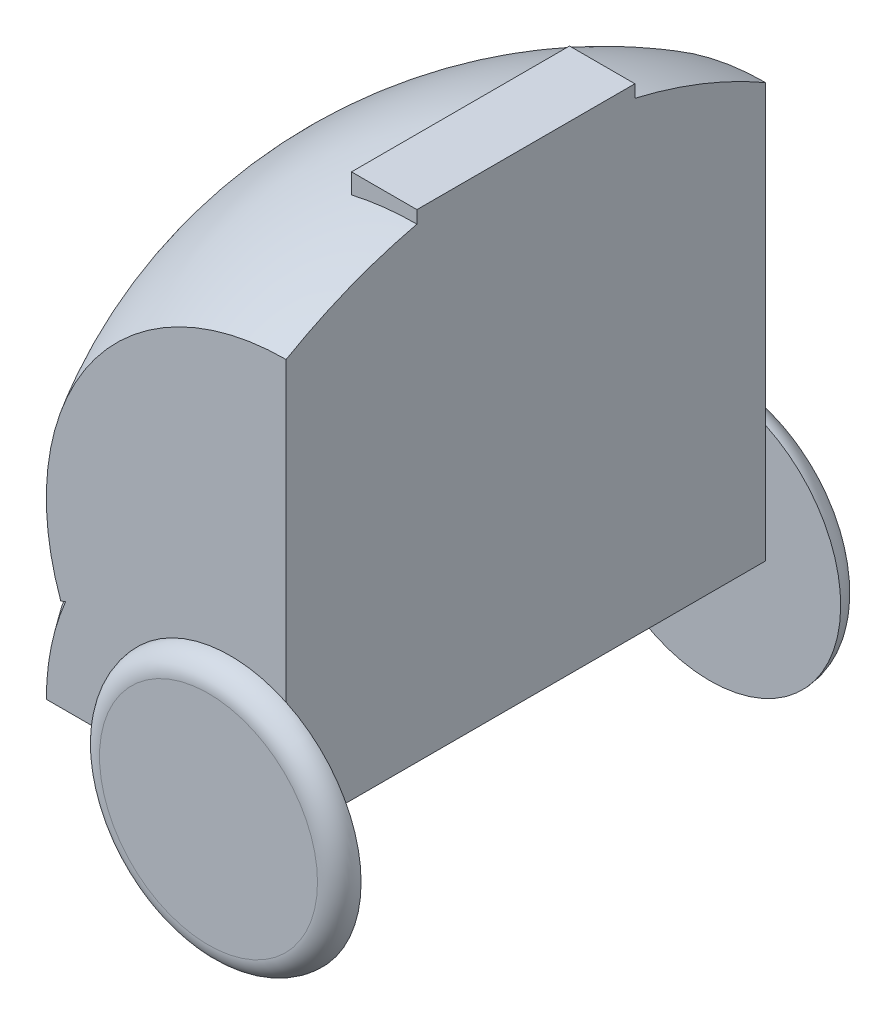
SolidWorks part; units mm, degrees
ref_plane "Płaszczyzna przednia" through (0, 0, 0) normal (0, 0, 1) x (1, 0, 0)
ref_plane "Płaszczyzna górna" through (0, 0, 0) normal (0, 1, 0) x (1, 0, 0)
ref_plane "Płaszczyzna prawa" through (0, 0, 0) normal (1, 0, 0) x (0, 0, -1)
sketch "Szkic1" plane through (0, 0, 0) normal (0, 1, 0) x (1, 0, 0)
  line L1 (-20, -55) -> (-20, 55)
  line L2 (-20, 55) -> (-75, 55)
  line L3 (-20, -55) -> (-75, -55)
  arc A0 (-75, 55) -> (-75, -55) centre (0, 0) ccw
  dimension "D3" = 55
revolve "Obrót1" add sketch "Szkic1" angle 90 about L1
sketch "Szkic2" plane through (-20, 0, 0) normal (1, 0, 0) x (0, 0, -1)
  line L0 (-55, 55) -> (-55, 40)
  line L1 (-55, 55) -> (-55, 0) construction
  line L2 (-55, 40) -> (55, 40)
  line L3 (55, 0) -> (55, 55) construction
  line L4 (-55, 55) -> (-55, 95)
  line L5 (0, 40) -> (0, 60.5329) construction
  line L6 (55, 55) -> (55, 40)
  line L7 (55, 55) -> (55, 95)
  arc A0 (55, 95) -> (-55, 95) centre (0, 0) ccw
  dimension "D1" = 15
  dimension "D2" = 40
revolve "Obrót2" add sketch "Szkic2" angle 110 about L2 reverse direction yes
sketch "Szkic3" plane through (-20, 0, 0) normal (1, 0, 0) x (0, 0, -1)
  line L0 (0, 109.7725) -> (-25, 109.7725)
  line L1 (-25, 109.7725) -> (-25, 99.7725)
  line L2 (-25, 99.7725) -> (25, 99.7725)
  line L3 (25, 99.7725) -> (25, 109.7725)
  line L4 (25, 109.7725) -> (0, 109.7725)
  arc A0 (55, 95) -> (-55, 95) centre (0, 0) ccw construction
  dimension "D1" = 25
  dimension "D2" = 10
  dimension "D3" = 50
  dimension "D4" = 10
extrude "Dodanie-wyciągnięcie1" add sketch "Szkic3" against normal blind 15
sketch "Szkic4" plane through (0, 109.7725, 0) normal (0, 1, 0) x (1, 0, 0)
  line L0 (-20, -25) -> (-100.2748, -46.5096)
  line L1 (-35, -25) -> (-20, -25) construction
  dimension "D1" = 15
sketch "Szkic5" plane through (0, 0, 55) normal (0, 0, 1) x (1, 0, 0)
  circle A0 centre (-32.8029, -0.2275) radius 30
  dimension "D1" = 60
extrude "Dodanie-wyciągnięcie2" add sketch "Szkic5" along normal blind 5
fillet "Zaokrąglenie1" radius 5 1 edges at (-2.8029, -0.2275, 60)
sketch "Szkic6" plane through (0, 0, -55) normal (0, 0, -1) x (-1, 0, 0)
  circle A0 centre (32.8029, -0.2275) radius 30
  dimension "D1" = 60
extrude "Dodanie-wyciągnięcie3" add sketch "Szkic6" along normal blind 5
fillet "Zaokrąglenie2" radius 5 1 edges at (-62.8029, -0.2275, -60)
